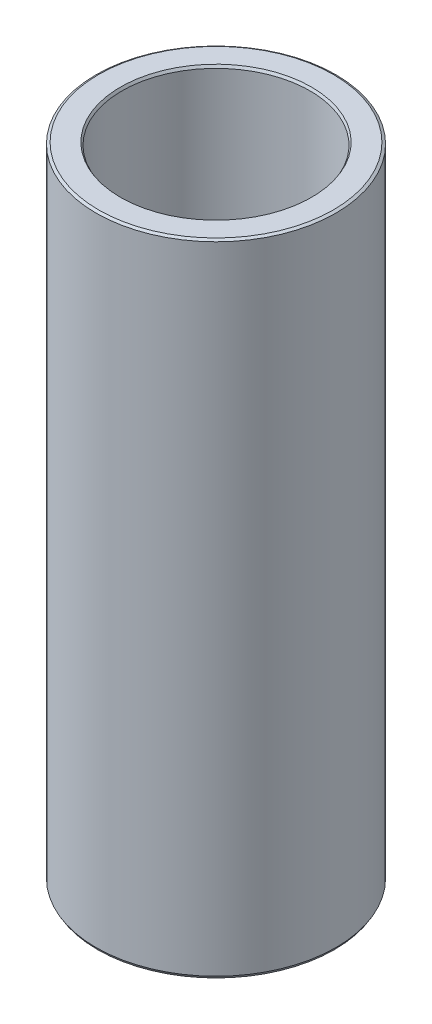
SolidWorks part; units mm, degrees
ref_plane "Front Plane" through (0, 0, 0) normal (0, 0, 1) x (1, 0, 0)
ref_plane "Top Plane" through (0, 0, 0) normal (0, 1, 0) x (1, 0, 0)
ref_plane "Right Plane" through (0, 0, 0) normal (1, 0, 0) x (0, 0, -1)
sketch "Sketch1" plane through (0, 0, 0) normal (0, 1, 0) x (1, 0, 0)
  circle A0 centre (0, 0) radius 60
  dimension "SLEEVE_OD" = 120
extrude "Boss-Extrude1" add sketch "Sketch1" along normal blind 320.3009
sketch "Sketch2" plane through (0, 0, 0) normal (0, 1, 0) x (1, 0, 0)
  circle A0 centre (0, 0) radius 47.0793
  dimension "BORE_D" = 94.1586
extrude "Cut-Extrude1" cut sketch "Sketch2" along normal through all
chamfer "Chamfer1" distance 0.7397 angle 60 4 edges at (0, 320.3009, 47.0793) (0, 0, 47.0793) (0, 0, 60) (0, 320.3009, 60) first distance on face at (0, 320.3009, 47.0793) first distance on face at (0, 0, 47.0793) first distance on face at (0, 320.3009, 60)
